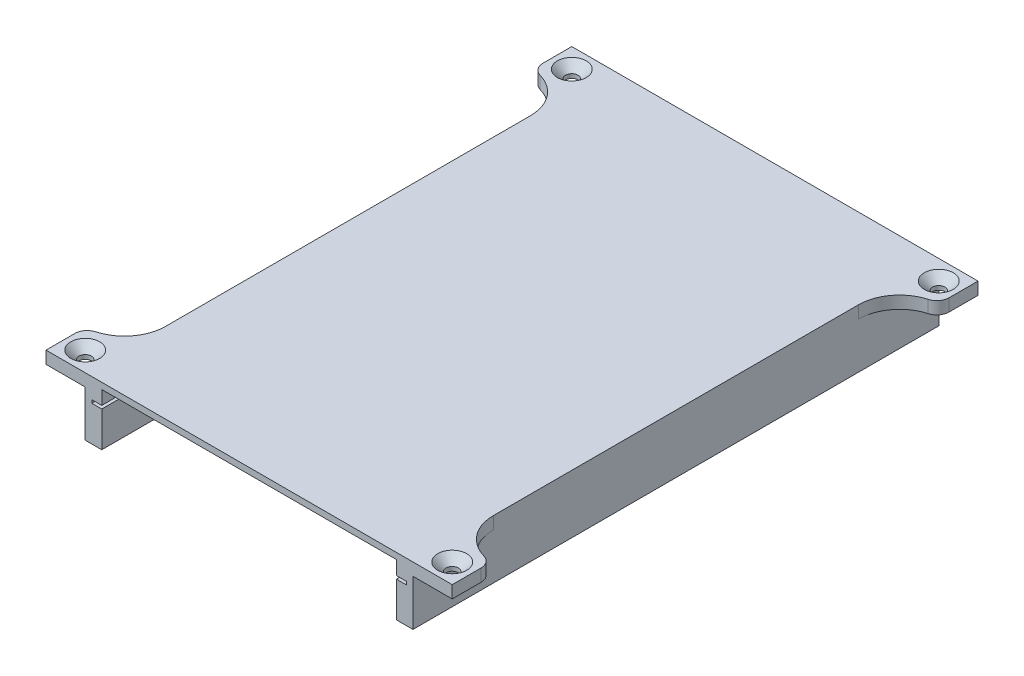
SolidWorks part; units mm, degrees
material "PLA"
ref_plane "Спереди" through (0, 0, 0) normal (0, 0, 1) x (1, 0, 0)
ref_plane "Сверху" through (0, 0, 0) normal (0, 1, 0) x (1, 0, 0)
ref_plane "Справа" through (0, 0, 0) normal (1, 0, 0) x (0, 0, -1)
sketch "Эскиз1" plane through (0, 0, 0) normal (0, 1, 0) x (1, 0, 0)
  line L0 (0, 0) -> (-4740.9496, 0) construction
  line L1 (0, 0) -> (0, -4740.9496) construction
  line L2 (35.675, 63.65) -> (39.675, 63.65)
  line L3 (-35.675, -63.65) -> (-39.675, -63.65)
  line L4 (-35.675, -63.65) -> (-35.675, 63.65)
  line L5 (-35.675, 63.65) -> (-39.675, 63.65)
  line L6 (-39.675, -63.65) -> (-39.675, 63.65)
  line L7 (-35.675, -63.65) -> (-39.675, 63.65) construction
  line L8 (-35.675, 63.65) -> (-39.675, -63.65) construction
  line L9 (39.675, -63.65) -> (39.675, 63.65)
  line L10 (35.675, -63.65) -> (39.675, -63.65)
  line L11 (35.675, -63.65) -> (35.675, 63.65)
  line L12 (35.675, 63.65) -> (39.675, -63.65) construction
  line L13 (35.675, -63.65) -> (39.675, 63.65) construction
  point P5 (-37.675, 0)
  point P14 (37.675, 0)
  dimension "D1" = 4
  dimension "D2" = 127.3
  dimension "D3" = 71.35
extrude "Бобышка-Вытянуть1" add sketch "Эскиз1" along normal blind 12.65
sketch "Эскиз2" plane through (0, 12.65, 0) normal (0, 1, 0) x (1, 0, 0)
  line L1 (39.675, 63.65) -> (-39.675, 63.65)
  line L2 (39.675, 63.65) -> (39.675, -63.65)
  line L3 (39.675, -63.65) -> (-39.675, -63.65)
  line L4 (-39.675, 63.65) -> (-39.675, -63.65)
extrude "Бобышка-Вытянуть2" add sketch "Эскиз2" along normal blind 1.5
sketch "Эскиз3" plane through (0, 0, -63.65) normal (0, 0, -1) x (-1, 0, 0)
  line L0 (0, 0) -> (0, 50000) construction
  line L1 (-35.675, 12.65) -> (-35.675, 0) construction
  line L2 (-35.675, 9.3) -> (-38.075, 9.3)
  line L3 (-35.675, 9.3) -> (-35.675, 8.55)
  line L4 (-35.675, 8.55) -> (-38.075, 8.55)
  line L5 (-38.075, 9.3) -> (-38.075, 8.55)
  line L6 (35.675, 8.55) -> (38.075, 8.55)
  line L7 (38.075, 9.3) -> (38.075, 8.55)
  line L8 (35.675, 9.3) -> (38.075, 9.3)
  line L9 (35.675, 9.3) -> (35.675, 8.55)
  line L10 (-39.675, 0) -> (-35.675, 0) construction
  dimension "D1" = 2.4
  dimension "D2" = 0.75
  dimension "D3" = 8.55
extrude "Вырез-Вытянуть1" cut sketch "Эскиз3" against normal through all from offset 1.5 offset against normal yes
sketch "Эскиз4" plane through (0, 12.65, 0) normal (0, -1, 0) x (1, 0, 0)
  line L0 (35.675, -63.65) -> (35.675, 63.65) construction
  line L1 (-35.675, -63.65) -> (35.675, -63.65)
  line L2 (-35.675, -63.65) -> (-35.675, -62.15)
  line L3 (-35.675, -62.15) -> (35.675, -62.15)
  line L4 (35.675, -63.65) -> (35.675, -62.15)
  dimension "D1" = 1.5
extrude "Бобышка-Вытянуть3" add sketch "Эскиз4" along normal up to surface (12.65 mm away) up to face at (37.675, 0, 0)
sketch "Эскиз5" plane through (0, 14.15, 0) normal (0, 1, 0) x (1, 0, 0)
  line L0 (0, 0) -> (0, 50000) construction
  line L1 (0, 0) -> (-50000, 0) construction
  line L2 (-49.175, 63.65) -> (-39.675, 54.15) construction
  line L3 (-39.675, 63.65) -> (-49.175, 63.65)
  line L4 (-39.675, 63.65) -> (-39.675, 54.15)
  line L5 (-39.675, 54.15) -> (-49.175, 54.15)
  line L6 (-49.175, 63.65) -> (-49.175, 54.15)
  line L7 (-39.675, 63.65) -> (-49.175, 54.15) construction
  line L8 (-39.675, -63.65) -> (-49.175, -54.15) construction
  line L9 (-49.175, -63.65) -> (-39.675, -54.15) construction
  line L10 (-49.175, -63.65) -> (-49.175, -54.15)
  line L11 (-39.675, -54.15) -> (-49.175, -54.15)
  line L12 (-39.675, -63.65) -> (-39.675, -54.15)
  line L13 (-39.675, -63.65) -> (-49.175, -63.65)
  line L14 (49.175, -63.65) -> (39.675, -54.15) construction
  line L15 (39.675, -63.65) -> (49.175, -54.15) construction
  line L16 (39.675, 63.65) -> (49.175, 54.15) construction
  line L17 (49.175, 63.65) -> (39.675, 54.15) construction
  line L18 (39.675, -63.65) -> (49.175, -63.65)
  line L19 (39.675, -63.65) -> (39.675, -54.15)
  line L20 (39.675, -54.15) -> (49.175, -54.15)
  line L21 (49.175, -63.65) -> (49.175, -54.15)
  line L22 (49.175, 63.65) -> (49.175, 54.15)
  line L23 (39.675, 54.15) -> (49.175, 54.15)
  line L24 (39.675, 63.65) -> (39.675, 54.15)
  line L25 (39.675, 63.65) -> (49.175, 63.65)
  circle A0 centre (-44.425, 58.9) radius 1.5
  circle A1 centre (-44.425, 58.9) radius 2.75 construction
  circle A2 centre (-44.425, -58.9) radius 2.75 construction
  circle A3 centre (-44.425, -58.9) radius 1.5
  circle A4 centre (44.425, -58.9) radius 2.75 construction
  circle A5 centre (44.425, 58.9) radius 2.75 construction
  circle A6 centre (44.425, -58.9) radius 1.5
  circle A7 centre (44.425, 58.9) radius 1.5
  dimension "D1" = 3
  dimension "D2" = 5.5
  dimension "D3" = 2
  dimension "D4" = 2
extrude "Бобышка-Вытянуть4" add sketch "Эскиз5" against normal blind 3
chamfer "Фаска1" distance 2 angle 45 4 edges at (44.425, 14.15, 60.4) (-44.425, 14.15, 57.4) (44.425, 14.15, -60.4) (-44.425, 14.15, -57.4)
fillet "Скругление1" radius 10 4 edges at (39.675, 12.65, 54.15) (39.675, 12.65, -54.15) (-39.675, 12.65, 54.15) (-39.675, 12.65, -54.15)
fillet "Скругление2" radius 3 4 edges at (-49.175, 12.65, 54.15) (49.175, 12.65, 54.15) (49.175, 12.65, -54.15) (-49.175, 12.65, -54.15)
sketch "Эскиз6" plane through (0, 12.65, 0) normal (0, -1, 0) x (1, 0, 0)
  line L0 (35.675, -62.15) -> (35.675, 63.65) construction
  line L1 (32.175, -52.5) -> (24.975, -52.5)
  line L2 (32.175, -52.5) -> (32.175, -62.15)
  line L3 (32.175, -59.7) -> (24.975, -59.7) construction
  line L4 (24.975, -52.5) -> (24.975, -62.15)
  line L5 (32.175, -52.5) -> (24.975, -59.7) construction
  line L6 (32.175, -59.7) -> (24.975, -52.5) construction
  line L7 (35.675, -62.15) -> (-35.675, -62.15) construction
  line L8 (32.175, -62.15) -> (24.975, -62.15)
  circle A0 centre (28.575, -56.1) radius 2.1 construction
  point P0 (28.575, -56.1)
  dimension "D3" = 4.2
  dimension "D4" = 1.5
  dimension "D5" = 1.5
  dimension "D1" = 7.1
  dimension "D2" = 6.05
extrude "Бобышка-Вытянуть5" add sketch "Эскиз6" along normal blind 9.6
sketch "Эскиз7" plane through (0, 3.05, 0) normal (0, -1, 0) x (1, 0, 0)
  line L0 (24.975, -52.5) -> (32.175, -59.7) construction
  line L1 (32.175, -52.5) -> (24.975, -59.7) construction
  line L2 (32.175, -62.15) -> (32.175, -52.5) construction
  line L3 (24.975, -52.5) -> (24.975, -62.15) construction
  circle A0 centre (28.575, -56.1) radius 2.05
  dimension "D1" = 4.1
extrude "Вырез-Вытянуть2" cut sketch "Эскиз7" against normal blind 4.5
sketch "Эскиз8" plane through (0, 0, 0) normal (0, -1, 0) x (1, 0, 0)
  line L0 (-35.675, 63.65) -> (-35.675, -62.15) construction
  line L1 (-35.675, 38.05) -> (-38.075, 38.05)
  line L2 (-35.675, 38.05) -> (-35.675, 32.2)
  line L3 (-35.675, 32.2) -> (-38.075, 32.2)
  line L4 (-38.075, 38.05) -> (-38.075, 32.2)
  line L5 (0, 0) -> (0, 50000) construction
  line L6 (-35.675, -16.55) -> (-38.075, -16.55)
  line L7 (-35.675, -16.55) -> (-35.675, -22.4)
  line L8 (-35.675, -22.4) -> (-38.075, -22.4)
  line L9 (-38.075, -16.55) -> (-38.075, -22.4)
  line L10 (-39.675, 63.65) -> (-35.675, 63.65) construction
  line L11 (35.675, -22.4) -> (38.075, -22.4)
  line L12 (38.075, -16.55) -> (38.075, -22.4)
  line L13 (35.675, -16.55) -> (38.075, -16.55)
  line L14 (35.675, -16.55) -> (35.675, -22.4)
  line L15 (35.675, 32.2) -> (38.075, 32.2)
  line L16 (38.075, 38.05) -> (38.075, 32.2)
  line L17 (35.675, 38.05) -> (38.075, 38.05)
  line L18 (35.675, 38.05) -> (35.675, 32.2)
  line L19 (39.675, -63.65) -> (-39.675, -63.65) construction
  point P26 (0, -63.65)
  dimension "D1" = 2.4
  dimension "D2" = 5.85
  dimension "D3" = 48.75
  dimension "D4" = 25.6
extrude "Вырез-Вытянуть3" cut sketch "Эскиз8" against normal up to surface (8.55 mm away) up to face at (-36.875, 8.55, 0.75)
sketch "Эскиз10" plane through (0, 12.65, 0) normal (0, -1, 0) x (1, 0, 0)
  line L0 (-35.675, 63.65) -> (-35.675, -62.15) construction
  line L1 (-25.275, -51.75) -> (-28.275, -51.75)
  line L2 (-25.275, -51.75) -> (-25.275, -57.7)
  line L3 (-25.275, -57.7) -> (-28.275, -57.7)
  line L4 (-28.275, -51.75) -> (-28.275, -57.7)
  line L5 (24.975, -62.15) -> (-35.675, -62.15) construction
  line L6 (35.675, -62.15) -> (-35.675, -62.15) construction
  line L8 (15.225, -51.75) -> (18.225, -51.75)
  line L9 (15.225, -51.75) -> (15.225, -57.7)
  line L10 (15.225, -57.7) -> (18.225, -57.7)
  line L11 (18.225, -51.75) -> (18.225, -57.7)
  dimension "D1" = 10.4
  dimension "D2" = 4.45
  dimension "D3" = 10.4
  dimension "D4" = 3
  dimension "D5" = 50.9
extrude "Бобышка-Вытянуть6" add sketch "Эскиз10" along normal blind 3.95
sketch "Эскиз11" plane through (0, 12.65, 0) normal (0, -1, 0) x (1, 0, 0)
  line L1 (-25.275, -57.7) -> (15.225, -57.7)
  line L2 (-25.275, -57.7) -> (-25.275, -51.75)
  line L3 (-25.275, -51.75) -> (15.225, -51.75)
  line L4 (15.225, -57.7) -> (15.225, -51.75)
extrude "Бобышка-Вытянуть7" add sketch "Эскиз11" along normal blind 0.35
fillet "Скругление4" radius 4 1 edges at (-5.025, 12.65, -57.7)
fillet "Скругление5" radius 2 2 edges at (-26.775, 8.7, -57.7) (16.725, 8.7, -57.7)
sketch "Эскиз12" plane through (0, 0, -62.15) normal (0, 0, 1) x (1, 0, 0)
  line L0 (24.975, 12.65) -> (-35.675, 12.65) construction
  line L1 (15.475, 8) -> (-25.525, 8)
  line L2 (15.475, 8) -> (15.475, 12.65)
  line L12 (15.475, 12.65) -> (-25.525, 12.65)
  line L13 (-25.525, 8) -> (-25.525, 12.65)
  line L15 (-5.025, 12.3) -> (-5.025, 12.65) construction
  line L17 (-25.275, 12.3) -> (15.225, 12.3) construction
  point P12 (-5.2496, 12.1881)
  point P13 (-5.025, 12.3)
  dimension "D1" = 4.65
  dimension "D2" = 41
extrude "Вырез-Вытянуть4" cut sketch "Эскиз12" against normal through all
